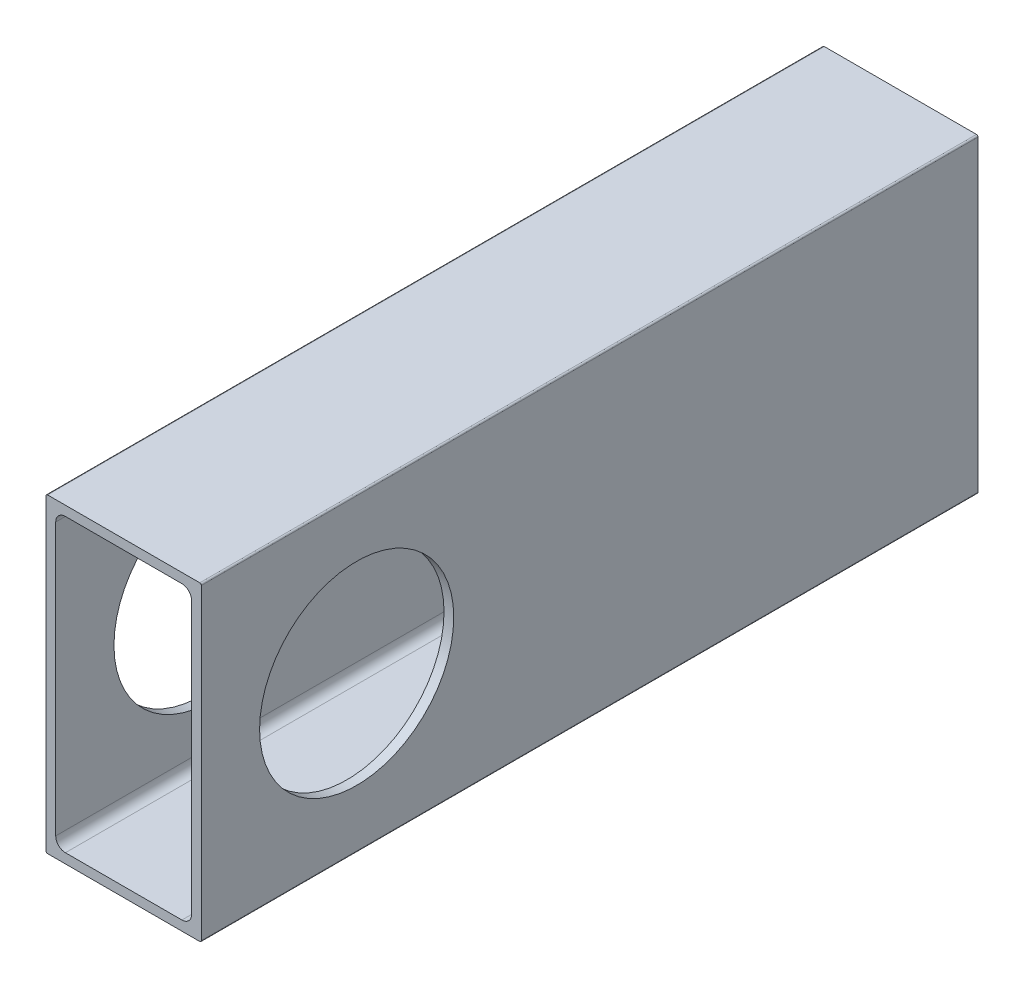
SolidWorks part; units mm, degrees
material "1060 Alloy"
ref_plane "Front Plane" through (0, 0, 0) normal (0, 0, 1) x (1, 0, 0)
ref_plane "Top Plane" through (0, 0, 0) normal (0, 1, 0) x (1, 0, 0)
ref_plane "Right Plane" through (0, 0, 0) normal (1, 0, 0) x (0, 0, -1)
ref_plane "Plane1" through (0, 0, 0) normal (0, 0, -1) x (-1, 0, 0)
sketch "Sketch1" plane through (0, 0, 0) normal (0, 0, -1) x (-1, 0, 0)
  line L0 (-11.1125, -22.225) -> (-11.1125, 22.225)
  line L1 (-9.525, 23.8125) -> (9.525, 23.8125)
  line L2 (11.1125, 22.225) -> (11.1125, -22.225)
  line L3 (9.525, -23.8125) -> (-9.525, -23.8125)
  line L4 (-12.7, 25.146) -> (-12.7, -25.146)
  line L5 (-12.446, -25.4) -> (12.446, -25.4)
  line L6 (12.7, -25.146) -> (12.7, 25.146)
  line L7 (12.446, 25.4) -> (-12.446, 25.4)
  arc A0 (-11.1125, 22.225) -> (-9.525, 23.8125) centre (-9.525, 22.225) cw
  arc A1 (9.525, 23.8125) -> (11.1125, 22.225) centre (9.525, 22.225) cw
  arc A2 (11.1125, -22.225) -> (9.525, -23.8125) centre (9.525, -22.225) cw
  arc A3 (-9.525, -23.8125) -> (-11.1125, -22.225) centre (-9.525, -22.225) cw
  arc A4 (-12.7, -25.146) -> (-12.446, -25.4) centre (-12.446, -25.146) ccw
  arc A5 (12.446, -25.4) -> (12.7, -25.146) centre (12.446, -25.146) ccw
  arc A6 (12.7, 25.146) -> (12.446, 25.4) centre (12.446, 25.146) ccw
  arc A7 (-12.446, 25.4) -> (-12.7, 25.146) centre (-12.446, 25.146) ccw
extrude "Boss-Extrude1" add sketch "Sketch1" against normal blind 127
sketch "Sketch2" plane through (12.7, 0, 0) normal (1, 0, 0) x (0, 0, -1)
  line L0 (-127, 0) -> (-101.6, 0) construction
  line L1 (-127, 25.146) -> (-127, -25.146) construction
  circle A0 centre (-101.6, 0) radius 15.875
  dimension "D1" = 31.75
  dimension "D2" = 25.4
extrude "Cut-Extrude1" cut sketch "Sketch2" against normal blind 25.4
